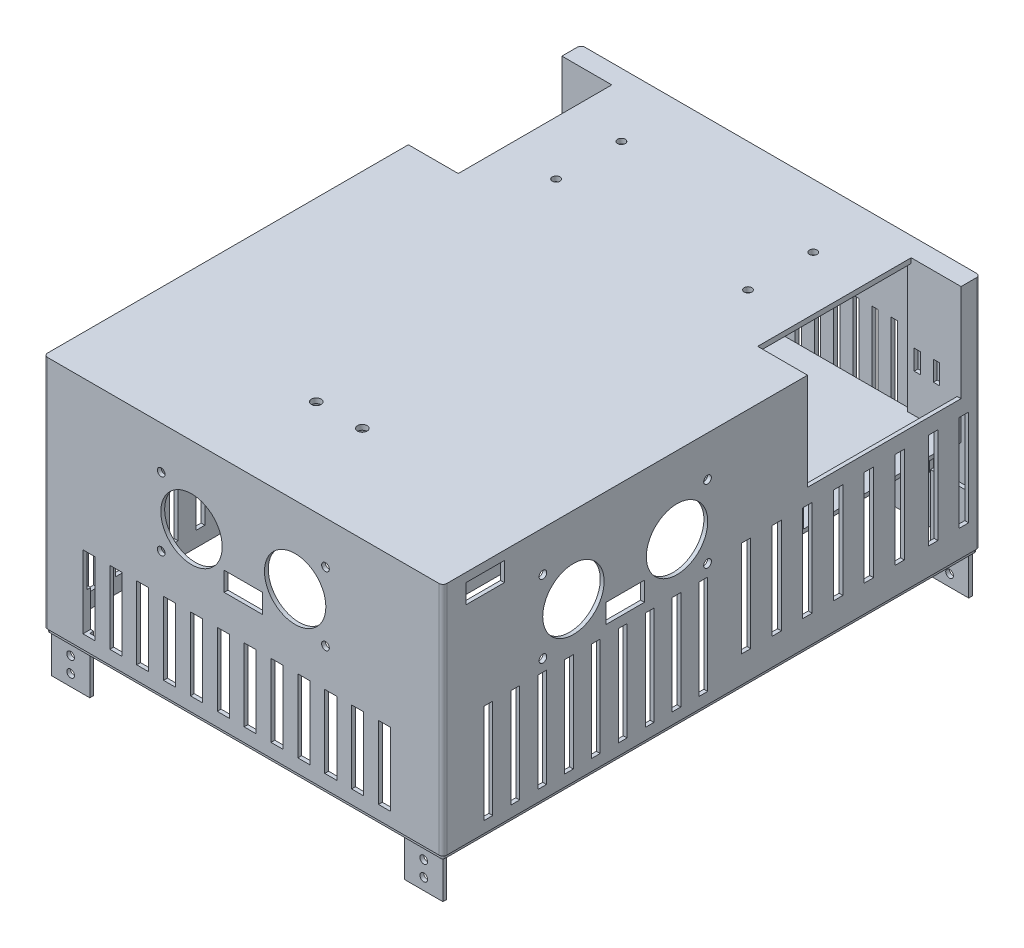
SolidWorks part; units mm, degrees
ref_plane "Front Plane" through (0, 0, 0) normal (0, 0, 1) x (1, 0, 0)
ref_plane "Top Plane" through (0, 0, 0) normal (0, 1, 0) x (1, 0, 0)
ref_plane "Right Plane" through (0, 0, 0) normal (1, 0, 0) x (0, 0, -1)
sketch "Sketch1" plane through (0, 0, 0) normal (0, 1, 0) x (1, 0, 0)
  line L0 (0, 0) -> (0, 70) construction
  line L1 (-52, 70) -> (52, 70)
  line L2 (-52, 70) -> (-52, 65)
  line L3 (-52, -70) -> (52, -70)
  line L4 (52, 70) -> (52, 65)
  line L5 (-52, 70) -> (52, -70) construction
  line L6 (-52, -70) -> (52, 70) construction
  line L7 (0, 0) -> (0, -70) construction
  line L8 (52, 65) -> (39, 65)
  line L9 (39, 65) -> (39, 25)
  line L10 (39, 25) -> (52, 25)
  line L11 (-39, 25) -> (-52, 25)
  line L12 (-52, 65) -> (-39, 65)
  line L13 (-39, 65) -> (-39, 25)
  line L14 (52, 25) -> (52, -70)
  line L15 (-52, 25) -> (-52, -70)
  point P0 (0, 0)
  dimension "D1" = 140
  dimension "100" = 104
  dimension "D3" = 40
  dimension "D4" = 5
  dimension "D5" = 13
extrude "Boss-Extrude1" add sketch "Sketch1" along normal blind 1.3
sketch "Sketch2" plane through (0, 1.3, 0) normal (0, 1, 0) x (1, 0, 0)
  line L0 (-39, 45) -> (-25, 45) construction
  line L1 (-39, 65) -> (-39, 25) construction
  line L2 (39, 25) -> (39, 65) construction
  line L7 (0, 0) -> (0, 70) construction
  line L8 (52, 70) -> (-52, 70) construction
  line L13 (25, 45) -> (39, 45) construction
  circle A0 centre (-25, 36.5) radius 1
  circle A1 centre (-25, 53.5) radius 1
  circle A2 centre (25, 36.5) radius 1
  circle A3 centre (25, 53.5) radius 1
  point P11 (25, 45)
  dimension "D3" = 2
  dimension "D4" = 2
  dimension "D5" = 2
  dimension "D6" = 2
  dimension "D2" = 8.5
extrude "Cut-Extrude3" cut sketch "Sketch2" against normal through all
sketch "Sketch3" plane through (0, 0, 0) normal (0, -1, 0) x (1, 0, 0)
  line L12 (52, -25) -> (52, 70)
  line L13 (52, 70) -> (-52, 70)
  line L14 (-52, 70) -> (-52, -25)
  line L15 (-52, -25) -> (-39, -25)
  line L16 (-39, -25) -> (-39, -65)
  line L17 (-39, -65) -> (-52, -65)
  line L18 (-52, -65) -> (-52, -70)
  line L19 (-52, -70) -> (52, -70)
  line L20 (52, -70) -> (52, -65)
  line L21 (52, -65) -> (39, -65)
  line L22 (39, -65) -> (39, -25)
  line L23 (39, -25) -> (52, -25)
  line L24 (51, -24) -> (51, 69)
  line L25 (51, 69) -> (-51, 69)
  line L26 (-51, 69) -> (-51, -24)
  line L27 (-51, -24) -> (-38, -24)
  line L28 (-38, -24) -> (-38, -66)
  line L29 (-38, -66) -> (-51, -66)
  line L30 (-51, -66) -> (-51, -69)
  line L31 (-51, -69) -> (51, -69)
  line L32 (51, -69) -> (51, -66)
  line L33 (51, -66) -> (38, -66)
  line L34 (38, -66) -> (38, -24)
  line L35 (38, -24) -> (51, -24)
  line L36 (51, -24) -> (51, 69)
  line L37 (51, 69) -> (-51, 69)
  line L38 (-51, 69) -> (-51, -24)
  line L39 (-51, -24) -> (-38, -24)
  line L40 (-38, -24) -> (-38, -66)
  line L41 (-38, -66) -> (-51, -66)
  line L42 (-51, -66) -> (-51, -69)
  line L43 (-51, -69) -> (51, -69)
  line L44 (51, -69) -> (51, -66)
  line L45 (51, -66) -> (38, -66)
  line L46 (38, -66) -> (38, -24)
  line L47 (38, -24) -> (51, -24)
  dimension "D1" = 1
  dimension "D2" = 1
extrude "Boss-Extrude3" add sketch "Sketch3" along normal blind 60
sketch "Sketch5" plane through (-52, 0, 0) normal (-1, 0, 0) x (0, 0, 1)
  line L0 (22.5, 1.3) -> (22.5, -51.1049) construction
  line L1 (-25, 1.3) -> (70, 1.3) construction
  line L2 (22.5, 1.3) -> (45, 1.3)
  line L7 (45, 1.3) -> (45, -18.7)
  line L10 (0, 1.3) -> (22.5, 1.3)
  line L11 (0, -8.7) -> (45, -8.7) construction
  line L12 (45, -18.7) -> (0, -18.7) construction
  line L13 (0, -27.8356) -> (0.1053, -27.8356)
  line L14 (2.0101, -28.4431) -> (2.0101, -28.7)
  line L15 (22.5, -28.7) -> (27.5, -28.7)
  line L16 (27.5, -28.7) -> (27.5, -23.7)
  line L17 (27.5, -23.7) -> (17.5, -23.7)
  line L18 (17.5, -23.7) -> (17.5, -28.7)
  line L19 (17.5, -28.7) -> (22.5, -28.7)
  line L20 (27.5, -28.7) -> (17.5, -28.7)
  line L21 (0, -18.7) -> (0, 1.3)
  circle A0 centre (9, -18.7) radius 8
  circle A1 centre (36, -18.7) radius 8
  circle A2 centre (1.0502, -28.1628) radius 1
  circle A3 centre (43.9498, -28.1628) radius 1
  circle A4 centre (1.0502, -9.2372) radius 1
  circle A5 centre (43.9498, -9.2372) radius 1
  point P16 (22.5, -24.9024)
  dimension "D6" = 16
  dimension "D7" = 16
  dimension "D12" = 2
  dimension "D1" = 22.5
  dimension "D2" = 22.5
  dimension "D4" = 10
  dimension "D8" = 13.5
  dimension "D9" = 13.5
  dimension "D10" = 1.1
  dimension "D11" = 1.1
  dimension "D13" = 5
  dimension "D14" = 5
  dimension "D15" = 5
  dimension "D16" = 10
extrude "Cut-Extrude5" cut sketch "Sketch5" against normal through all both and the other way through all contours A0 | A5 | A3 | A4 | L14 A2 L13 | L19 L15 L16 L17 L18 | A1 region at (-52, -18.7, 9) region at (-52, -28.1628, 1.0502) region at (-52, -28.1628, 43.9498) region at (-52, -9.2372, 1.0502) region at (-52, -9.2372, 43.9498)
sketch "Sketch7" plane through (0, 0, 70) normal (0, 0, 1) x (1, 0, 0)
  line L0 (0, 0) -> (0, -60) construction
  line L1 (52, -60) -> (-52, -60) construction
  line L2 (0, 1.3) -> (22.5, 1.3) construction
  line L3 (-52, 1.3) -> (52, 1.3) construction
  line L4 (22.5, 1.3) -> (22.5, -28.7) construction
  line L5 (22.5, -28.7) -> (0, -28.7) construction
  line L6 (0, -28.7) -> (-22.5, -28.7) construction
  line L7 (-22.5, -28.7) -> (-22.5, 1.3) construction
  line L8 (-22.5, 1.3) -> (0, 1.3) construction
  line L9 (-22.5, -8.7) -> (22.5, -8.7) construction
  line L10 (-22.5, -18.7) -> (22.5, -18.7) construction
  line L11 (-22.5, -27.6) -> (-21.4, -27.6) construction
  line L12 (-21.4, -27.6) -> (-21.4, -28.7) construction
  line L13 (0, -28.7) -> (5, -28.7)
  line L14 (5, -28.7) -> (5, -23.7)
  line L15 (5, -23.7) -> (-5, -23.7)
  line L16 (-5, -23.7) -> (-5, -28.7)
  line L17 (-5, -28.7) -> (0, -28.7)
  circle A0 centre (-13.5, -18.7) radius 8
  circle A1 centre (13.5, -18.7) radius 8
  circle A2 centre (-21.4, -27.6) radius 1
  circle A3 centre (21.4, -27.6) radius 1
  circle A4 centre (21.4, -9.8) radius 1
  circle A5 centre (-21.4, -9.8) radius 1
  point P21 (0, -30)
  dimension "D6" = 16
  dimension "D7" = 16
  dimension "D12" = 2
  dimension "D1" = 22.5
  dimension "D2" = 22.5
  dimension "D3" = 30
  dimension "D4" = 10
  dimension "D5" = 10
  dimension "D8" = 13.5
  dimension "D9" = 13.5
  dimension "D10" = 1.1
  dimension "D11" = 1.1
  dimension "D13" = 5
  dimension "D14" = 5
  dimension "D15" = 5
extrude "Cut-Extrude6" cut sketch "Sketch7" against normal blind 31.3
sketch "Sketch8" plane through (0, 1.3, 0) normal (0, 1, 0) x (1, 0, 0)
  line L0 (0, -70) -> (0, 70) construction
  line L1 (-52, -70) -> (52, -70) construction
  line L2 (52, 70) -> (-52, 70) construction
  line L3 (52, -45) -> (-52, -45) construction
  line L4 (52, -70) -> (52, 25) construction
  line L5 (-52, 25) -> (-52, -70) construction
  circle A0 centre (-6, -45) radius 1.25
  circle A1 centre (6, -45) radius 1.25
  dimension "D2" = 2.5
  dimension "D3" = 2.5
  dimension "D1" = 25
  dimension "D4" = 6
  dimension "D5" = 6
extrude "Cut-Extrude10" cut sketch "Sketch8" against normal through all contours A0 | A1 region at (-6, 1.3, 45)
sketch "Sketch10" plane through (39, 0, 0) normal (1, 0, 0) x (0, 0, -1)
  line L0 (25, 1.3) -> (65, 1.3) construction
  line L2 (65, 1.3) -> (65, -60) construction
  line L3 (65, -24) -> (25, -24)
  line L4 (25, 1.3) -> (25, -60) construction
  line L5 (25, -24) -> (25, 0)
  line L6 (25, 0) -> (65, 0)
  line L7 (65, 0) -> (65, -24)
  dimension "D1" = 1.3
  dimension "D2" = 24
extrude "Cut-Extrude11" cut sketch "Sketch10" against normal through all
sketch "Sketch11" plane through (-39, 0, 0) normal (-1, 0, 0) x (0, 0, 1)
  line L0 (-25, -24) -> (-65, -24)
  line L1 (-65, -24) -> (-65, -25)
  line L2 (-65, -24) -> (-65, -60) construction
  line L3 (-65, -25) -> (-25, -25)
  line L4 (-25, -24) -> (-25, -60) construction
  line L5 (-25, -25) -> (-25, -24)
extrude "Boss-Extrude4" add sketch "Sketch11" along normal through all
sketch "Sketch12" plane through (-39, 0, 0) normal (-1, 0, 0) x (0, 0, 1)
  line L0 (-25, -60) -> (-65, -60)
  line L1 (-65, -60) -> (-65, -25)
  line L2 (-65, -25) -> (-65, -60) construction
  line L3 (-65, -25) -> (-25, -25)
  line L4 (-25, -25) -> (-25, -60) construction
  line L5 (-25, -25) -> (-25, -60)
extrude "Cut-Extrude12" cut sketch "Sketch12" against normal through all
sketch "Sketch13" plane through (0, -25, 0) normal (0, -1, 0) x (1, 0, 0)
  line L0 (-52, -25) -> (-51, -25)
  line L1 (-52, -25) -> (-38, -25) construction
  line L2 (-51, -25) -> (-51, -65)
  line L3 (-51, -65) -> (-52, -65)
  line L4 (-52, -65) -> (-52, -25)
  dimension "D1" = 1
extrude "Boss-Extrude5" add sketch "Sketch13" along normal through all
sketch "Sketch14" plane through (39, 0, 0) normal (1, 0, 0) x (0, 0, -1)
  line L0 (25, -25) -> (25, -24)
  line L1 (25, -24) -> (25, -25) construction
  line L2 (25, -24) -> (65, -24) construction
  line L3 (25, -24) -> (65, -24)
  line L4 (65, -24) -> (65, -25)
  line L5 (65, -25) -> (25, -25)
extrude "Boss-Extrude6" add sketch "Sketch14" along normal through all
sketch "Sketch15" plane through (0, -25, 0) normal (0, -1, 0) x (1, 0, 0)
  line L0 (52, -25) -> (52, -65)
  line L1 (52, -65) -> (51, -65)
  line L2 (52, -65) -> (38, -65) construction
  line L3 (51, -65) -> (51, -25)
  line L4 (52, -25) -> (38, -25) construction
  line L5 (51, -25) -> (52, -25)
  line L6 (51, -25) -> (52, -25)
  dimension "D1" = 1
extrude "Boss-Extrude8" add sketch "Sketch15" along normal through all contours L5 L0 L1 L3
sketch "Sketch17" plane through (0, 0, -25) normal (0, 0, -1) x (-1, 0, 0)
  line L0 (51, -25) -> (38, -25)
  line L1 (51, -25) -> (38, -25) construction
  line L2 (38, -25) -> (38, -60)
  line L6 (51, -25) -> (51, -60)
  line L7 (51, -60) -> (51, -25) construction
  line L8 (51, -60) -> (38, -60)
extrude "Cut-Extrude15" cut sketch "Sketch17" against normal up to next
sketch "Sketch18" plane through (0, 0, -65) normal (0, 0, 1) x (1, 0, 0)
  line L0 (-38, -25) -> (-38, -60)
  line L1 (-38, -60) -> (-51, -60) construction
  line L2 (-38, -60) -> (-38, -25) construction
  line L3 (-38, -60) -> (-51, -60)
  line L4 (-51, -60) -> (-51, -25) construction
  line L5 (-51, -60) -> (-51, -25)
  line L6 (-51, -25) -> (-38, -25)
extrude "Cut-Extrude16" cut sketch "Sketch18" against normal up to next
sketch "Sketch19" plane through (0, 0, -65) normal (0, 0, 1) x (1, 0, 0)
  line L0 (51, -60) -> (38, -60)
  line L1 (51, -60) -> (51, -25) construction
  line L2 (38, -60) -> (38, -25)
  line L3 (38, -25) -> (51, -25)
  line L4 (51, -25) -> (51, -60)
extrude "Cut-Extrude17" cut sketch "Sketch19" against normal up to next
sketch "Sketch20" plane through (0, 0, -25) normal (0, 0, -1) x (-1, 0, 0)
  line L0 (-38, -60) -> (-51, -60)
  line L1 (-51, -60) -> (-51, -25)
  line L2 (-51, -60) -> (-51, -25) construction
  line L3 (-51, -25) -> (-38, -25)
  line L4 (-38, -25) -> (-38, -60)
extrude "Cut-Extrude18" cut sketch "Sketch20" against normal up to next
sketch "Sketch21" plane through (38, 0, 0) normal (-1, 0, 0) x (0, 0, 1)
  line L0 (-66, -25) -> (-24, -25)
  line L1 (-24, -25) -> (-24, -24.1522)
  line L2 (-24, -25) -> (-24, 0) construction
  line L3 (-24, -24.1522) -> (-24, -23.9836)
  line L4 (-24, -23.9836) -> (-25, -24)
  line L5 (-25, -24) -> (-66, -24)
  line L6 (-66, -25) -> (-66, 0) construction
  line L7 (-66, -24) -> (-66, -25)
extrude "Boss-Extrude9" add sketch "Sketch21" along normal up to next
sketch "Sketch23" plane through (0, -25, 0) normal (0, -1, 0) x (1, 0, 0)
  line L0 (51, -45) -> (-51, -45) construction
  line L1 (51, -66) -> (51, -24) construction
  line L2 (-51, -66) -> (-51, -24) construction
  line L3 (24.9189, -50.7378) -> (24.8618, -66)
  line L4 (51, -66) -> (-51, -66) construction
  line L5 (24.8618, -66) -> (24.8618, -24) construction
  line L6 (-51, -24) -> (51, -24) construction
  line L7 (51, -69) -> (51, 69) construction
  line L9 (20.2368, -30.6694) -> (29.4868, -30.6694)
  line L10 (20.2368, -30.6694) -> (20.2368, -59.3306)
  line L11 (20.2368, -59.3306) -> (29.4868, -59.3306)
  line L12 (29.4868, -30.6694) -> (29.4868, -59.3306)
  line L13 (20.2368, -30.6694) -> (29.4868, -59.3306) construction
  line L14 (20.2368, -59.3306) -> (29.4868, -30.6694) construction
  point P15 (24.8618, -45)
  dimension "D1" = 26.1382
  dimension "D2" = 9.25
  dimension "D3" = 28.6611
extrude "Cut-Extrude19" cut sketch "Sketch23" against normal up to next contours L12 L9 L10 L11 region at (24.8618, -25, -45)
sketch "Sketch24" plane through (0, 0, 0) normal (0, -1, 0) x (1, 0, 0)
  line L0 (-24.9942, -66) -> (-24.9942, -24) construction
  line L1 (51, -66) -> (-51, -66) construction
  line L2 (-51, -24) -> (51, -24) construction
  line L3 (-51, -45) -> (51, -45) construction
  line L4 (-51, -66) -> (-51, -24) construction
  line L5 (51, -66) -> (51, -24) construction
  line L6 (0, -66) -> (0, -24) construction
sketch "Sketch25" plane through (0, 0, 0) normal (0, -1, 0) x (1, 0, 0)
  line L0 (-24.9942, -66) -> (-24.9942, -24) construction
  line L1 (-20.3691, -59.3306) -> (-29.6192, -59.3306)
  line L2 (-20.3691, -59.3306) -> (-20.3691, -30.6694)
  line L3 (-20.3691, -30.6694) -> (-29.6192, -30.6694)
  line L4 (-29.6192, -59.3306) -> (-29.6192, -30.6694)
  line L5 (-20.3691, -59.3306) -> (-29.6192, -30.6694) construction
  line L6 (-20.3691, -30.6694) -> (-29.6192, -59.3306) construction
  line L7 (20.2368, -30.6694) -> (29.4868, -30.6694) construction
  point P0 (-24.9942, -45)
extrude "Cut-Extrude20" cut sketch "Sketch25" along normal up to next
fillet "Fillet2" radius 1 4 edges at (52, -29.35, -70) (-52, -29.35, -70) (-52, -29.35, 70) (52, -29.35, 70)
sketch "Sketch31" plane through (51, 0, 0) normal (-1, 0, 0) x (0, 0, 1)
  line L0 (-24, -25) -> (69, -24.188) construction
  line L1 (69, -60) -> (69, 0) construction
sketch "Sketch34" plane through (0, -60, 0) normal (0, -1, 0) x (1, 0, 0)
  line L4 (-51, -69) -> (51, -69)
  line L5 (51, -69) -> (51, 69)
  line L6 (51, 69) -> (-51, 69)
  line L7 (-51, 69) -> (-51, -69)
  line L8 (-51, -69.5) -> (51, -69.5)
  line L9 (-51, -69.5) -> (51, -69.5)
  line L10 (51.5, -69) -> (51.5, 69)
  line L11 (51.5, -69) -> (51.5, 69)
  line L16 (51, 69.5) -> (-51, 69.5)
  line L17 (51, 69.5) -> (-51, 69.5)
  line L18 (-51.5, 69) -> (-51.5, -69)
  line L19 (-51.5, 69) -> (-51.5, -69)
  arc A4 (51, -69.5) -> (51.5, -69) centre (51, -69) ccw
  arc A5 (51, -69.5) -> (51.5, -69) centre (51, -69) ccw
  arc A6 (51.5, 69) -> (51, 69.5) centre (51, 69) ccw
  arc A7 (51.5, 69) -> (51, 69.5) centre (51, 69) ccw
  arc A8 (-51, 69.5) -> (-51.5, 69) centre (-51, 69) ccw
  arc A9 (-51, 69.5) -> (-51.5, 69) centre (-51, 69) ccw
  arc A10 (-51.5, -69) -> (-51, -69.5) centre (-51, -69) ccw
  arc A11 (-51.5, -69) -> (-51, -69.5) centre (-51, -69) ccw
  dimension "D1" = 0.5
sketch "Sketch35" plane through (0, 0, -70) normal (0, 0, -1) x (-1, 0, 0)
  line L0 (0, 0) -> (0, -18.7) construction
  line L1 (45.2093, -48.7) -> (43.5805, -48.7)
  line L2 (43.5805, -48.7) -> (43.5805, -18.7)
  line L3 (43.5805, -18.7) -> (45.2093, -18.7)
  line L4 (45.2093, -18.7) -> (45.2093, -48.7)
  line L5 (44.3949, -48.7) -> (44.3949, -60) construction
  line L6 (51, -60) -> (-51, -60) construction
  line L7 (44.3949, -18.7) -> (44.3949, 1.3) construction
  line L8 (-51, 1.3) -> (51, 1.3) construction
  line L9 (40.2093, -18.7) -> (40.2093, -48.7)
  line L10 (38.5805, -48.7) -> (38.5805, -18.7)
  line L11 (40.2093, -48.7) -> (38.5805, -48.7)
  line L12 (38.5805, -18.7) -> (40.2093, -18.7)
  line L13 (35.2093, -18.7) -> (35.2093, -48.7)
  line L14 (33.5805, -48.7) -> (33.5805, -18.7)
  line L15 (35.2093, -48.7) -> (33.5805, -48.7)
  line L16 (33.5805, -18.7) -> (35.2093, -18.7)
  line L17 (30.2093, -18.7) -> (30.2093, -48.7)
  line L18 (28.5805, -48.7) -> (28.5805, -18.7)
  line L19 (30.2093, -48.7) -> (28.5805, -48.7)
  line L20 (28.5805, -18.7) -> (30.2093, -18.7)
  line L21 (25.2093, -18.7) -> (25.2093, -48.7)
  line L22 (23.5805, -48.7) -> (23.5805, -18.7)
  line L23 (25.2093, -48.7) -> (23.5805, -48.7)
  line L24 (23.5805, -18.7) -> (25.2093, -18.7)
  line L25 (20.2093, -18.7) -> (20.2093, -48.7)
  line L26 (18.5805, -48.7) -> (18.5805, -18.7)
  line L27 (20.2093, -48.7) -> (18.5805, -48.7)
  line L28 (18.5805, -18.7) -> (20.2093, -18.7)
  line L29 (15.2093, -18.7) -> (15.2093, -48.7)
  line L30 (13.5805, -48.7) -> (13.5805, -18.7)
  line L31 (15.2093, -48.7) -> (13.5805, -48.7)
  line L32 (13.5805, -18.7) -> (15.2093, -18.7)
  line L33 (10.2093, -18.7) -> (10.2093, -48.7)
  line L34 (8.5805, -48.7) -> (8.5805, -18.7)
  line L35 (10.2093, -48.7) -> (8.5805, -48.7)
  line L36 (8.5805, -18.7) -> (10.2093, -18.7)
  line L37 (5.2093, -18.7) -> (5.2093, -48.7)
  line L38 (3.5805, -48.7) -> (3.5805, -18.7)
  line L39 (5.2093, -48.7) -> (3.5805, -48.7)
  line L40 (3.5805, -18.7) -> (5.2093, -18.7)
  line L41 (0.2093, -18.7) -> (0.2093, -48.7)
  line L42 (-1.4195, -48.7) -> (-1.4195, -18.7)
  line L43 (0.2093, -48.7) -> (-1.4195, -48.7)
  line L44 (-1.4195, -18.7) -> (0.2093, -18.7)
  line L45 (-4.7907, -18.7) -> (-4.7907, -48.7)
  line L46 (-6.4195, -48.7) -> (-6.4195, -18.7)
  line L47 (-4.7907, -48.7) -> (-6.4195, -48.7)
  line L48 (-6.4195, -18.7) -> (-4.7907, -18.7)
  line L49 (-9.7907, -18.7) -> (-9.7907, -48.7)
  line L50 (-11.4195, -48.7) -> (-11.4195, -18.7)
  line L51 (-9.7907, -48.7) -> (-11.4195, -48.7)
  line L52 (-11.4195, -18.7) -> (-9.7907, -18.7)
  line L53 (-14.7907, -18.7) -> (-14.7907, -48.7)
  line L54 (-16.4195, -48.7) -> (-16.4195, -18.7)
  line L55 (-14.7907, -48.7) -> (-16.4195, -48.7)
  line L56 (-16.4195, -18.7) -> (-14.7907, -18.7)
  line L57 (-19.7907, -18.7) -> (-19.7907, -48.7)
  line L58 (-21.4195, -48.7) -> (-21.4195, -18.7)
  line L59 (-19.7907, -48.7) -> (-21.4195, -48.7)
  line L60 (-21.4195, -18.7) -> (-19.7907, -18.7)
  line L61 (-24.7907, -18.7) -> (-24.7907, -48.7)
  line L62 (-26.4195, -48.7) -> (-26.4195, -18.7)
  line L63 (-24.7907, -48.7) -> (-26.4195, -48.7)
  line L64 (-26.4195, -18.7) -> (-24.7907, -18.7)
  line L65 (-29.7907, -18.7) -> (-29.7907, -48.7)
  line L66 (-31.4195, -48.7) -> (-31.4195, -18.7)
  line L67 (-29.7907, -48.7) -> (-31.4195, -48.7)
  line L68 (-31.4195, -18.7) -> (-29.7907, -18.7)
  line L69 (-34.7907, -18.7) -> (-34.7907, -48.7)
  line L70 (-36.4195, -48.7) -> (-36.4195, -18.7)
  line L71 (-34.7907, -48.7) -> (-36.4195, -48.7)
  line L72 (-36.4195, -18.7) -> (-34.7907, -18.7)
  line L73 (-39.7907, -18.7) -> (-39.7907, -48.7)
  line L74 (-41.4195, -48.7) -> (-41.4195, -18.7)
  line L75 (-39.7907, -48.7) -> (-41.4195, -48.7)
  line L76 (-41.4195, -18.7) -> (-39.7907, -18.7)
  line L77 (-44.7907, -18.7) -> (-44.7907, -48.7)
  line L78 (-46.4195, -48.7) -> (-46.4195, -18.7)
  line L79 (-44.7907, -48.7) -> (-46.4195, -48.7)
  line L80 (-46.4195, -18.7) -> (-44.7907, -18.7)
  line L82 (-8, -5.3873) -> (8, -5.3873)
  line L83 (-8, -5.3873) -> (-8, -12.3873)
  line L84 (-8, -12.3873) -> (8, -12.3873)
  line L85 (8, -5.3873) -> (8, -12.3873)
  line L86 (-8, -5.3873) -> (8, -12.3873) construction
  line L87 (-8, -12.3873) -> (8, -5.3873) construction
  point P87 (0, -8.8873)
  dimension "D2" = 20
  dimension "D3" = 30
  dimension "D4" = 16
  dimension "D5" = 7
  dimension "D1" = 19
extrude "Cut-Extrude22" cut sketch "Sketch35" against normal blind 5
sketch "Sketch36" plane through (52, 0, 0) normal (1, 0, 0) x (0, 0, -1)
  line L0 (66.9781, -53) -> (64.524, -53)
  line L1 (64.524, -53) -> (64.524, -28)
  line L3 (66.9781, -28) -> (66.9781, -53)
  line L4 (48.9744, -53) -> (48.9744, -60) construction
  line L5 (69, -60) -> (-69, -60) construction
  line L6 (57.7511, -53) -> (57.7511, -60) construction
  line L8 (58.9781, -28) -> (58.9781, -53)
  line L9 (56.524, -53) -> (56.524, -28)
  line L10 (58.9781, -53) -> (56.524, -53)
  line L12 (50.2015, -53) -> (50.2015, -31.3061)
  line L13 (50.2015, -31.3061) -> (50.2015, -28)
  line L14 (50.2015, -28) -> (47.7473, -28)
  line L15 (47.7473, -28) -> (47.7473, -53)
  line L16 (47.7473, -53) -> (50.2015, -53)
  line L18 (56.524, -28) -> (58.9781, -28)
  line L19 (42.2015, -53) -> (42.2015, -31.3061)
  line L20 (39.7473, -28) -> (39.7473, -53)
  line L21 (42.2015, -28) -> (39.7473, -28)
  line L22 (42.2015, -31.3061) -> (42.2015, -28)
  line L23 (39.7473, -53) -> (42.2015, -53)
  line L24 (34.2015, -53) -> (34.2015, -31.3061)
  line L25 (31.7473, -28) -> (31.7473, -53)
  line L26 (34.2015, -28) -> (31.7473, -28)
  line L27 (34.2015, -31.3061) -> (34.2015, -28)
  line L28 (31.7473, -53) -> (34.2015, -53)
  line L29 (26.2015, -53) -> (26.2015, -31.3061)
  line L30 (23.7473, -28) -> (23.7473, -53)
  line L31 (26.2015, -28) -> (23.7473, -28)
  line L32 (26.2015, -31.3061) -> (26.2015, -28)
  line L33 (23.7473, -53) -> (26.2015, -53)
  line L34 (18.2015, -53) -> (18.2015, -31.3061)
  line L35 (15.7473, -28) -> (15.7473, -53)
  line L36 (18.2015, -28) -> (15.7473, -28)
  line L37 (18.2015, -31.3061) -> (18.2015, -28)
  line L38 (15.7473, -53) -> (18.2015, -53)
  line L39 (10.2015, -53) -> (10.2015, -31.3061)
  line L40 (7.7473, -28) -> (7.7473, -53)
  line L41 (10.2015, -28) -> (7.7473, -28)
  line L42 (10.2015, -31.3061) -> (10.2015, -28)
  line L43 (7.7473, -53) -> (10.2015, -53)
  line L44 (64.524, -28) -> (66.9781, -28)
  dimension "D3" = 25
  dimension "D4" = 25
  dimension "D5" = 7
  dimension "D1" = 2
  dimension "D2" = 6
extrude "Cut-Extrude23" cut sketch "Sketch36" against normal through all
extrude "Boss-Extrude13" add sketch "Sketch34" along normal blind 1
sketch "Sketch39" plane through (0, 0, -69) normal (0, 0, 1) x (1, 0, 0)
  line L1 (51, -61) -> (51, 0) construction
  line L6 (51, -61) -> (51, -47)
  line L7 (51, -47) -> (41, -47)
  line L8 (41, -47) -> (41, -61)
  line L9 (-51, -61) -> (51, -61) construction
  line L10 (41, -61) -> (51, -61)
  dimension "D1" = 10
  dimension "D2" = 14
extrude "Boss-Extrude14" add sketch "Sketch39" along normal blind 1
sketch "Sketch40" plane through (0, -61, 0) normal (0, -1, 0) x (1, 0, 0)
  line L0 (41, -68) -> (41, -69.5)
  line L1 (-51, -69.5) -> (51, -69.5) construction
  line L2 (41, -69.5) -> (51, -69.5)
  line L6 (41, -68) -> (51, -68)
  line L7 (51, -68) -> (51, -69.5)
extrude "Boss-Extrude15" add sketch "Sketch40" along normal blind 10 contours L2 L0 L6 L7
sketch "Sketch41" plane through (0, 0, -69.5) normal (0, 0, -1) x (-1, 0, 0)
  line L0 (-46, -71) -> (-46, -61) construction
  line L1 (-41, -71) -> (-51, -71) construction
  line L2 (-41, -61) -> (-51, -61) construction
sketch "Sketch42" plane through (0, 0, 69) normal (0, 0, -1) x (-1, 0, 0)
  line L0 (-51, -61) -> (-51, -47)
  line L1 (-51, -61) -> (-51, 0) construction
  line L2 (-51, -47) -> (-41, -47)
  line L3 (-41, -47) -> (-41, -61)
  line L4 (-51, -61) -> (51, -61) construction
  line L5 (-41, -61) -> (-51, -61)
  dimension "D1" = 10
  dimension "D2" = 14
extrude "Boss-Extrude16" add sketch "Sketch42" along normal blind 1
sketch "Sketch43" plane through (0, -61, 0) normal (0, -1, 0) x (1, 0, 0)
  line L0 (41, 68) -> (41, 69)
  line L1 (51, 68) -> (41, 68) construction
  line L4 (50.9987, 68) -> (41, 68)
  line L5 (41, 69) -> (51, 69)
  line L6 (50.9987, 68) -> (51, 69)
extrude "Boss-Extrude17" add sketch "Sketch43" along normal blind 10
sketch "Sketch45" plane through (0, 0, -69.5) normal (0, 0, -1) x (-1, 0, 0)
  line L0 (-46, -71) -> (-46, -61) construction
  line L1 (-41, -61) -> (-51, -61)
  line L2 (-41, -64) -> (-51, -64) construction
  line L3 (-41, -71) -> (-41, -61) construction
  line L4 (-51, -71) -> (-51, -61) construction
  line L5 (-41, -68) -> (-51, -68) construction
  line L6 (-41, -71) -> (-51, -71) construction
  circle A0 centre (-46, -64) radius 1
  circle A1 centre (-46, -68) radius 1
  dimension "D3" = 2
  dimension "D4" = 2
  dimension "D1" = 3
  dimension "D2" = 3
extrude "Cut-Extrude24" cut sketch "Sketch45" against normal through all contours A0 | A1 region at (46, -64, -69.5) region at (46, -68, -69.5)
sketch "Sketch47" plane through (0, 0, -69) normal (0, 0, 1) x (1, 0, 0)
  line L7 (-41, -61) -> (-51, -61)
  line L8 (-51, -61) -> (41, -61) construction
  line L9 (-51, -61) -> (-51, -47)
  line L10 (-51, -61) -> (-51, 0) construction
  line L11 (-51, -47) -> (-41, -47)
  line L12 (-41, -47) -> (-41, -61)
  dimension "D1" = 10
  dimension "D2" = 14
extrude "Boss-Extrude18" add sketch "Sketch47" along normal blind 1
sketch "Sketch48" plane through (0, -61, 0) normal (0, -1, 0) x (1, 0, 0)
  line L0 (-51, -68) -> (-51, -69.5)
  line L1 (-51, -69.5) -> (-41, -69.5)
  line L2 (-51, -69.5) -> (41, -69.5) construction
  line L3 (-41, -69.5) -> (-41, -68)
  line L4 (-41, -68) -> (-51, -68)
extrude "Boss-Extrude19" add sketch "Sketch48" along normal blind 10
sketch "Sketch49" plane through (0, 0, -68) normal (0, 0, 1) x (1, 0, 0)
  line L0 (-46, -71) -> (-46, -47) construction
  line L1 (-41, -71) -> (-51, -71) construction
  line L2 (-41, -47) -> (-51, -47) construction
  line L3 (-41, -68) -> (-51, -68) construction
  line L4 (-41, -71) -> (-41, -47) construction
  line L6 (-41, -64) -> (-51, -64) construction
  line L7 (-51, -47) -> (-51, -61) construction
  line L8 (-51, -71) -> (-51, -61) construction
  circle A0 centre (-46, -64) radius 1
  circle A1 centre (-46, -68) radius 1
  dimension "D3" = 2
  dimension "D4" = 2
  dimension "D1" = 3
  dimension "D2" = 4
  dimension "D5" = 4
sketch "Sketch50" plane through (0, 0, 69) normal (0, 0, -1) x (-1, 0, 0)
  line L0 (51, -61) -> (51, -47)
  line L1 (51, -61) -> (51, 0) construction
  line L2 (51, -47) -> (41, -47)
  line L3 (41, -47) -> (41, -61)
  line L4 (-41, -61) -> (51, -61) construction
  line L5 (41, -61) -> (51, -61)
  dimension "D1" = 14
  dimension "D2" = 10
extrude "Boss-Extrude20" add sketch "Sketch50" along normal blind 1
sketch "Sketch51" plane through (0, -61, 0) normal (0, -1, 0) x (1, 0, 0)
  line L0 (-41, 68) -> (-41, 69)
  line L3 (-51, 69) -> (-51, 68)
  line L4 (-51, 68) -> (-41, 68)
  line L5 (-41, 69) -> (-51, 69)
extrude "Boss-Extrude21" add sketch "Sketch51" along normal blind 10
extrude "Cut-Extrude25" cut sketch "Sketch49" along normal through all both and the other way through all contours A0 | A1
sketch "Sketch56" plane through (0, 0, 0) normal (0, -1, 0) x (1, 0, 0)
  line L0 (0, 69) -> (0, -44.7759) construction
  line L1 (51, 69) -> (-51, 69) construction
  dimension "D1" = 113.7759
sketch "Sketch58" plane through (0, -25, 0) normal (0, -1, 0) x (1, 0, 0)
  line L0 (-51, -66) -> (-51, -24)
  line L1 (-51, -24) -> (51, -24)
  line L2 (51, -24) -> (51, -66)
  line L3 (51, -66) -> (-51, -66)
extrude "Cut-Extrude30" cut sketch "Sketch58" against normal blind 1.1
sketch "Sketch59" plane through (0, -23.9, 0) normal (0, -1, 0) x (1, 0, 0)
  line L0 (-51, -24) -> (-38, -24)
  line L1 (-38, -24) -> (-38, -25)
  line L2 (-38, -25) -> (-51, -25) construction
  line L3 (-38, -25) -> (-38, -24) construction
  line L4 (-38, -25) -> (-51, -25)
  line L5 (-51, -25) -> (-51, -24)
  line L6 (-51, -66) -> (-51, -65)
  line L7 (-51, -65) -> (-38, -65)
  line L8 (-38, -65) -> (-38, -66)
  line L9 (-38, -66) -> (-51, -66)
  line L10 (0, -65) -> (0, 68.8945) construction
  line L11 (38, -24) -> (38, -25)
  line L12 (51, -25) -> (51, -24)
  line L13 (38, -25) -> (51, -25)
  line L14 (51, -24) -> (38, -24)
  line L15 (38, -65) -> (38, -66)
  line L16 (51, -66) -> (51, -65)
  line L17 (38, -66) -> (51, -66)
  line L18 (51, -65) -> (38, -65)
extrude "Boss-Extrude22" add sketch "Sketch59" along normal blind 10
sketch "Sketch63" plane through (0, -33.9, 0) normal (0, -1, 0) x (1, 0, 0)
  line L0 (-51, -24) -> (51, -24)
  line L1 (51, -24) -> (51, -66)
  line L2 (51, -66) -> (51, -65) construction
  line L3 (51, -66) -> (-51, -66)
  line L4 (-51, -66) -> (-51, -24)
extrude "Boss-Extrude23" add sketch "Sketch63" along normal blind 1
sketch "Sketch66" plane through (0, -71, 0) normal (0, -1, 0) x (1, 0, 0)
  line L0 (41, -69.5) -> (51, -69.5)
  line L1 (41, -69.5) -> (51, -69.5) construction
  line L2 (51, -69.5) -> (51, -69)
  line L3 (51, -69) -> (41, -69)
  line L4 (41, -68) -> (41, -69.5) construction
  line L5 (41, -69) -> (41, -69.5)
extrude "Cut-Extrude31" cut sketch "Sketch66" against normal blind 10
sketch "Sketch67" plane through (0, -71, 0) normal (0, -1, 0) x (1, 0, 0)
  line L0 (-41, -69.5) -> (-51, -69.5)
  line L1 (-51, -69.5) -> (-51, -69)
  line L2 (-51, -69) -> (-41, -69)
  line L3 (-41, -69.5) -> (-41, -68) construction
  line L4 (-41, -69) -> (-41, -69.5)
extrude "Cut-Extrude32" cut sketch "Sketch67" against normal blind 10
sketch "Sketch68" plane through (0, 0, 70) normal (0, 0, 1) x (1, 0, 0)
  line L0 (31.3515, -37.4857) -> (28.2134, -56.448) construction
  line L1 (38.3515, -37.4857) -> (35.2134, -37.4857)
  line L2 (38.3515, -37.4857) -> (38.3515, -56.448)
  line L3 (38.3515, -56.448) -> (35.2134, -56.448)
  line L4 (35.2134, -37.4857) -> (35.2134, -56.448)
  line L5 (38.3515, -37.4857) -> (35.2134, -56.448) construction
  line L6 (38.3515, -56.448) -> (35.2134, -37.4857) construction
  line L7 (31.3515, -56.448) -> (28.2134, -37.4857) construction
  line L8 (31.3515, -37.4857) -> (31.3515, -56.448)
  line L9 (31.3515, -37.4857) -> (28.2134, -37.4857)
  line L10 (28.2134, -37.4857) -> (28.2134, -56.448)
  line L11 (31.3515, -56.448) -> (28.2134, -56.448)
  line L12 (24.3515, -37.4857) -> (21.2134, -56.448) construction
  line L13 (24.3515, -56.448) -> (21.2134, -37.4857) construction
  line L14 (24.3515, -37.4857) -> (24.3515, -56.448)
  line L15 (24.3515, -37.4857) -> (21.2134, -37.4857)
  line L16 (21.2134, -37.4857) -> (21.2134, -56.448)
  line L17 (24.3515, -56.448) -> (21.2134, -56.448)
  line L18 (17.3515, -37.4857) -> (14.2134, -56.448) construction
  line L19 (17.3515, -56.448) -> (14.2134, -37.4857) construction
  line L20 (17.3515, -37.4857) -> (17.3515, -56.448)
  line L21 (17.3515, -37.4857) -> (14.2134, -37.4857)
  line L22 (14.2134, -37.4857) -> (14.2134, -56.448)
  line L23 (17.3515, -56.448) -> (14.2134, -56.448)
  line L24 (10.3515, -37.4857) -> (7.2134, -56.448) construction
  line L25 (10.3515, -56.448) -> (7.2134, -37.4857) construction
  line L26 (10.3515, -37.4857) -> (10.3515, -56.448)
  line L27 (10.3515, -37.4857) -> (7.2134, -37.4857)
  line L28 (7.2134, -37.4857) -> (7.2134, -56.448)
  line L29 (10.3515, -56.448) -> (7.2134, -56.448)
  line L30 (3.3515, -37.4857) -> (0.2134, -56.448) construction
  line L31 (3.3515, -56.448) -> (0.2134, -37.4857) construction
  line L32 (3.3515, -37.4857) -> (3.3515, -56.448)
  line L33 (3.3515, -37.4857) -> (0.2134, -37.4857)
  line L34 (0.2134, -37.4857) -> (0.2134, -56.448)
  line L35 (3.3515, -56.448) -> (0.2134, -56.448)
  line L36 (-3.6485, -37.4857) -> (-6.7866, -56.448) construction
  line L37 (-3.6485, -56.448) -> (-6.7866, -37.4857) construction
  line L38 (-3.6485, -37.4857) -> (-3.6485, -56.448)
  line L39 (-3.6485, -37.4857) -> (-6.7866, -37.4857)
  line L40 (-6.7866, -37.4857) -> (-6.7866, -56.448)
  line L41 (-3.6485, -56.448) -> (-6.7866, -56.448)
  line L42 (-10.6485, -37.4857) -> (-13.7866, -56.448) construction
  line L43 (-10.6485, -56.448) -> (-13.7866, -37.4857) construction
  line L44 (-10.6485, -37.4857) -> (-10.6485, -56.448)
  line L45 (-10.6485, -37.4857) -> (-13.7866, -37.4857)
  line L46 (-13.7866, -37.4857) -> (-13.7866, -56.448)
  line L47 (-10.6485, -56.448) -> (-13.7866, -56.448)
  line L48 (-17.6485, -37.4857) -> (-20.7866, -56.448) construction
  line L49 (-17.6485, -56.448) -> (-20.7866, -37.4857) construction
  line L50 (-17.6485, -37.4857) -> (-17.6485, -56.448)
  line L51 (-17.6485, -37.4857) -> (-20.7866, -37.4857)
  line L52 (-20.7866, -37.4857) -> (-20.7866, -56.448)
  line L53 (-17.6485, -56.448) -> (-20.7866, -56.448)
  line L54 (-24.6485, -37.4857) -> (-27.7866, -56.448) construction
  line L55 (-24.6485, -56.448) -> (-27.7866, -37.4857) construction
  line L56 (-24.6485, -37.4857) -> (-24.6485, -56.448)
  line L57 (-24.6485, -37.4857) -> (-27.7866, -37.4857)
  line L58 (-27.7866, -37.4857) -> (-27.7866, -56.448)
  line L59 (-24.6485, -56.448) -> (-27.7866, -56.448)
  line L60 (-31.6485, -37.4857) -> (-34.7866, -56.448) construction
  line L61 (-31.6485, -56.448) -> (-34.7866, -37.4857) construction
  line L62 (-31.6485, -37.4857) -> (-31.6485, -56.448)
  line L63 (-31.6485, -37.4857) -> (-34.7866, -37.4857)
  line L64 (-34.7866, -37.4857) -> (-34.7866, -56.448)
  line L65 (-31.6485, -56.448) -> (-34.7866, -56.448)
  line L66 (-38.6485, -37.4857) -> (-41.7866, -56.448) construction
  line L67 (-38.6485, -56.448) -> (-41.7866, -37.4857) construction
  line L68 (-38.6485, -37.4857) -> (-38.6485, -56.448)
  line L69 (-38.6485, -37.4857) -> (-41.7866, -37.4857)
  line L70 (-41.7866, -37.4857) -> (-41.7866, -56.448)
  line L71 (-38.6485, -56.448) -> (-41.7866, -56.448)
  point P0 (36.7824, -46.9668)
  point P6 (29.7824, -46.9668)
  point P11 (22.7824, -46.9668)
  point P16 (15.7824, -46.9668)
  point P21 (8.7824, -46.9668)
  point P26 (1.7824, -46.9668)
  point P31 (-5.2176, -46.9668)
  point P36 (-12.2176, -46.9668)
  point P41 (-19.2176, -46.9668)
  point P46 (-26.2176, -46.9668)
  point P51 (-33.2176, -46.9668)
  point P56 (-40.2176, -46.9668)
  dimension "D1" = 12
extrude "Cut-Extrude33" cut sketch "Sketch68" against normal blind 10
sketch "Sketch69" plane through (52, 0, 0) normal (1, 0, 0) x (0, 0, -1)
  line L0 (-8.0186, -57.0473) -> (-10.2751, -57.0473)
  line L1 (-1.0186, -31.2389) -> (-3.2751, -31.2389)
  line L2 (-1.0186, -31.2389) -> (-1.0186, -57.0473)
  line L3 (-1.0186, -57.0473) -> (-3.2751, -57.0473)
  line L4 (-3.2751, -31.2389) -> (-3.2751, -57.0473)
  line L5 (-1.0186, -31.2389) -> (-3.2751, -57.0473) construction
  line L6 (-1.0186, -57.0473) -> (-3.2751, -31.2389) construction
  line L7 (-10.2751, -31.2389) -> (-10.2751, -57.0473)
  line L8 (-8.0186, -31.2389) -> (-8.0186, -57.0473)
  line L9 (-8.0186, -31.2389) -> (-10.2751, -31.2389)
  line L10 (-15.0186, -57.0473) -> (-17.2751, -57.0473)
  line L11 (-17.2751, -31.2389) -> (-17.2751, -57.0473)
  line L12 (-15.0186, -31.2389) -> (-15.0186, -57.0473)
  line L13 (-15.0186, -31.2389) -> (-17.2751, -31.2389)
  line L14 (-22.0186, -57.0473) -> (-24.2751, -57.0473)
  line L15 (-24.2751, -31.2389) -> (-24.2751, -57.0473)
  line L16 (-22.0186, -31.2389) -> (-22.0186, -57.0473)
  line L17 (-22.0186, -31.2389) -> (-24.2751, -31.2389)
  line L18 (-29.0186, -57.0473) -> (-31.2751, -57.0473)
  line L19 (-31.2751, -31.2389) -> (-31.2751, -57.0473)
  line L20 (-29.0186, -31.2389) -> (-29.0186, -57.0473)
  line L21 (-29.0186, -31.2389) -> (-31.2751, -31.2389)
  line L22 (-36.0186, -57.0473) -> (-38.2751, -57.0473)
  line L23 (-38.2751, -31.2389) -> (-38.2751, -57.0473)
  line L24 (-36.0186, -31.2389) -> (-36.0186, -57.0473)
  line L25 (-36.0186, -31.2389) -> (-38.2751, -31.2389)
  line L26 (-43.0186, -57.0473) -> (-45.2751, -57.0473)
  line L27 (-45.2751, -31.2389) -> (-45.2751, -57.0473)
  line L28 (-43.0186, -31.2389) -> (-43.0186, -57.0473)
  line L29 (-43.0186, -31.2389) -> (-45.2751, -31.2389)
  line L30 (-50.0186, -57.0473) -> (-52.2751, -57.0473)
  line L31 (-52.2751, -31.2389) -> (-52.2751, -57.0473)
  line L32 (-50.0186, -31.2389) -> (-50.0186, -57.0473)
  line L33 (-50.0186, -31.2389) -> (-52.2751, -31.2389)
  line L34 (-57.0186, -57.0473) -> (-59.2751, -57.0473)
  line L35 (-59.2751, -31.2389) -> (-59.2751, -57.0473)
  line L36 (-57.0186, -31.2389) -> (-57.0186, -57.0473)
  line L37 (-57.0186, -31.2389) -> (-59.2751, -31.2389)
  point P0 (-2.1469, -44.1431)
  dimension "D1" = 9
extrude "Cut-Extrude34" cut sketch "Sketch69" against normal through all
sketch "Sketch70" plane through (52, 0, 0) normal (1, 0, 0) x (0, 0, -1)
  line L0 (-64, -3.5127) -> (-69, -3.5127) construction
  line L1 (-64, -1.0127) -> (-54, -1.0127)
  line L2 (-64, -1.0127) -> (-64, -6.0127)
  line L3 (-64, -6.0127) -> (-54, -6.0127)
  line L4 (-54, -1.0127) -> (-54, -6.0127)
  line L5 (-64, -1.0127) -> (-54, -6.0127) construction
  line L6 (-64, -6.0127) -> (-54, -1.0127) construction
  line L7 (-69, 1.3) -> (-69, -60) construction
  point P0 (-59, -3.5127)
  dimension "D1" = 10
  dimension "D2" = 5
  dimension "D3" = 5
extrude "Cut-Extrude35" cut sketch "Sketch70" against normal blind 10
sketch "Sketch71" plane through (0, 0, -24) normal (0, 0, 1) x (1, 0, 0)
  line L2 (51.0786, 0) -> (38, 0) construction
  line L3 (51, -34.9) -> (38, -34.9) construction
  line L4 (51, -34.9) -> (-51, -34.9) construction
  dimension "D1" = 34.9
sketch "Sketch72" plane through (0, 0, 0) normal (0, -1, 0) x (1, 0, 0)
  line L0 (0, 69) -> (0, -44.7759) construction
  line L1 (20, 40.7094) -> (20.8, 40.7094)
  line L2 (20, 40.7094) -> (20, 15.7094)
  line L3 (20, 15.7094) -> (20.8, 15.7094)
  line L4 (20.8, 40.7094) -> (20.8, 15.7094)
  line L5 (20, 40.7094) -> (20.8, 15.7094) construction
  line L6 (20, 15.7094) -> (20.8, 40.7094) construction
  line L7 (0, 9.2465) -> (0, 18.0225) construction
  line L8 (-20, 15.7094) -> (-20.8, 15.7094)
  line L9 (-20, 40.7094) -> (-20, 15.7094)
  line L10 (-20, 40.7094) -> (-20.8, 15.7094) construction
  line L11 (-20.8, 40.7094) -> (-20.8, 15.7094)
  line L12 (-20, 40.7094) -> (-20.8, 40.7094)
  point P0 (20.4, 28.2094)
  point P14 (-20.4, 28.2094)
  dimension "D1" = 0.8
  dimension "D2" = 25
  dimension "D3" = 20
extrude "Boss-Extrude24" add sketch "Sketch72" along normal blind 34.9
